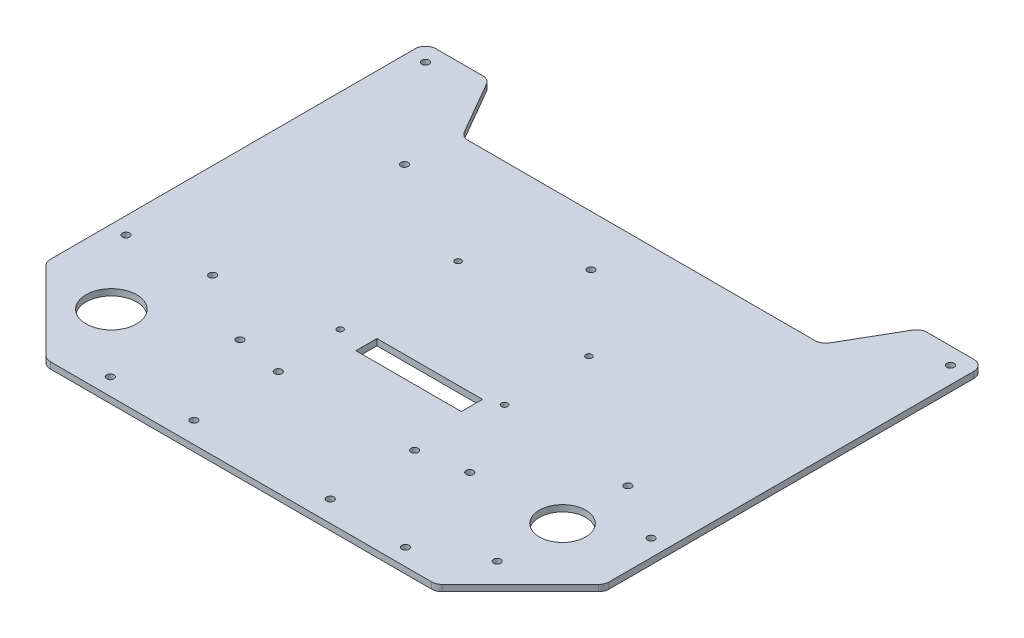
SolidWorks part; units mm, degrees
material "Acier non allié"
ref_plane "Front" through (0, 0, 0) normal (0, 0, 1) x (1, 0, 0)
ref_plane "Top" through (0, 0, 0) normal (0, 1, 0) x (1, 0, 0)
ref_plane "Right" through (0, 0, 0) normal (1, 0, 0) x (0, 0, -1)
sketch "Esquisse1" plane through (0, 0, 0) normal (0, 1, 0) x (1, 0, 0)
  line L0 (0, 0) -> (0, 1919.0564) construction
  line L1 (-92.5, 0) -> (92.5, 0)
  line L2 (92.5, 0) -> (132.5, 40)
  line L3 (132.5, 40) -> (132.5, 220)
  line L4 (132.5, 220) -> (102.5, 220)
  line L5 (102.5, 220) -> (85.1795, 190)
  line L6 (85.1795, 190) -> (-85.1795, 190)
  line L7 (-102.5, 220) -> (-85.1795, 190)
  line L8 (-132.5, 220) -> (-102.5, 220)
  line L9 (-132.5, 40) -> (-132.5, 220)
  line L10 (-92.5, 0) -> (-132.5, 40)
  point P12 (0, 190)
  dimension "D1" = 132.5
  dimension "D2" = 220
  dimension "D3" = 30
  dimension "D4" = 30
  dimension "D5" = 40
  dimension "D6" = 40
  dimension "D7" = 60
extrude "Boss.-Extru.1" add sketch "Esquisse1" along normal blind 3
fillet "Congé1" radius 5 10 edges at (132.5, 1.5, -220) (102.5, 1.5, -220) (85.1795, 1.5, -190) (-85.1795, 1.5, -190) (-102.5, 1.5, -220) (-132.5, 1.5, -220) (-132.5, 1.5, -40) (-92.5, 1.5, 0) (92.5, 1.5, 0) (132.5, 1.5, -40)
sketch "Esquisse2" plane through (0, 0, 0) normal (0, -1, 0) x (1, 0, 0)
  line L0 (0, 0) -> (0, -330.9968) construction
  line L1 (-90.4289, 0) -> (90.4289, 0) construction
  line L2 (-105.3868, -220) -> (-127.5, -220) construction
  line L3 (-132.5, -215) -> (-132.5, -42.0711) construction
  circle A0 centre (-70, -8) radius 1
  circle A1 centre (-124.5, -70) radius 1
  circle A2 centre (-124.5, -212) radius 1
  circle A3 centre (124.5, -212) radius 1
  circle A4 centre (124.5, -70) radius 1
  circle A5 centre (70, -8) radius 1
  dimension "D3" = 2
  dimension "D6" = 2
  dimension "D9" = 2
  dimension "D1" = 70
  dimension "D2" = 8
  dimension "D4" = 124.5
  dimension "D5" = 70
  dimension "D7" = 8
  dimension "D8" = 8
extrude "Enlèv. mat.-Extru.1" cut sketch "Esquisse2" against normal through all
hole_wizard "Dégagement M31" positions "Esquisse3" profile "Esquisse4" hole size "M3" standard "ISO" end condition through all
sketch "Esquisse3" plane through (0, 0, 0) normal (0, -1, 0) x (-1, 0, 0)
  point P0 (-70, 8)
  point P3 (-124.5, 70)
  point P6 (-124.5, 212)
  point P9 (124.5, 212)
  point P12 (124.5, 70)
  point P15 (70, 8)
sketch "Esquisse4" plane through (70, 0, -8) normal (1, 0, 0) x (0, 0, -1)
  line L0 (0, 0) -> (0, 3)
  line L1 (0, 3) -> (1.7, 3)
  line L2 (1.7, 3) -> (1.7, 0)
  line L5 (1.7, 0) -> (0, 0)
  line L11 (0, -6.35) -> (0, 107.95) construction
  dimension "Diamètre du perçage jusqu'au prochain" = 3.4
  dimension "Profondeur du perçage jusqu'au prochain" = 3
sketch "Esquisse5" plane through (0, 0, 0) normal (0, -1, 0) x (1, 0, 0)
  line L0 (-35, -138) -> (-35, -82) construction
  line L5 (35, -130) -> (35, -90) construction
  line L6 (132.5, -42.0711) -> (132.5, -215) construction
  line L7 (97.5, -86) -> (97.5, -24) construction
  line L20 (-132.5, -215) -> (-132.5, -42.0711) construction
  line L21 (-90.4289, 0) -> (90.4289, 0) construction
  line L22 (-105.3868, -220) -> (-127.5, -220) construction
  line L27 (-132.5, -215) -> (-132.5, -42.0711) construction
  line L28 (127.5, -220) -> (105.3868, -220) construction
  line L29 (-54.5, -54) -> (54.5, -54) construction
  line L30 (-54.5, -54) -> (-54.5, -166) construction
  line L31 (-54.5, -166) -> (54.5, -166) construction
  line L32 (54.5, -54) -> (54.5, -166) construction
  line L33 (-87.5, -74) -> (-87.5, -165) construction
  line L34 (-22.5, -87) -> (27.5, -87)
  line L35 (-22.5, -87) -> (-22.5, -77)
  line L36 (-22.5, -77) -> (27.5, -77)
  line L37 (27.5, -87) -> (27.5, -77)
  line L39 (127.5, -220) -> (105.3868, -220) construction
  line L40 (-32.335, -50) -> (32.335, -50) construction
  line L41 (-32.335, -50) -> (-32.335, -10) construction
  line L42 (-32.335, -10) -> (32.335, -10) construction
  line L43 (32.335, -50) -> (32.335, -10) construction
  circle A0 centre (-97.5, -36) radius 12
  circle A3 centre (97.5, -55) radius 11
  circle A4 centre (97.5, -86) radius 1.5
  circle A5 centre (97.5, -24) radius 1.5
  circle A6 centre (-35, -138) radius 1
  circle A7 centre (-35, -82) radius 1
  circle A8 centre (35, -130) radius 1
  circle A9 centre (35, -90) radius 1
  circle A10 centre (0, -166) radius 1.5
  circle A11 centre (-54.5, -54) radius 1.5
  circle A12 centre (54.5, -54) radius 1.5
  circle A13 centre (-87.5, -74) radius 1.5
  circle A14 centre (-87.5, -165) radius 1.5
  circle A15 centre (-32.335, -50) radius 1.5
  circle A16 centre (-32.335, -10) radius 1.5
  circle A17 centre (32.335, -10) radius 1.5
  circle A18 centre (32.335, -50) radius 1.5
  point P8 (97.5, -55)
  point P18 (-35, -110)
  point P23 (0, -166)
  point P29 (54.5, -110)
  point P47 (-22.5, -82)
  point P48 (2.5, -77)
  point P57 (0, 0)
  point P58 (0, -10)
  dimension "D10" = 24
  dimension "D2" = 22
  dimension "D6" = 3
  dimension "D7" = 3
  dimension "D20" = 2
  dimension "D21" = 2
  dimension "D27" = 2
  dimension "D28" = 2
  dimension "D14" = 3
  dimension "D30" = 3
  dimension "D31" = 3
  dimension "D38" = 3
  dimension "D39" = 3
  dimension "D19" = 3
  dimension "D36" = 3
  dimension "D40" = 3
  dimension "D41" = 3
  dimension "D8" = 35
  dimension "D9" = 36
  dimension "D3" = 35
  dimension "D4" = 55
  dimension "D5" = 62
  dimension "D22" = 110
  dimension "D23" = 97.5
  dimension "D24" = 56
  dimension "D25" = 8
  dimension "D26" = 40
  dimension "D29" = 70
  dimension "D11" = 109
  dimension "D12" = 112
  dimension "D13" = 110
  dimension "D32" = 50
  dimension "D33" = 10
  dimension "D34" = 135
  dimension "D35" = 91
  dimension "D37" = 55
  dimension "D15" = 45
  dimension "D16" = 64.67
  dimension "D17" = 40
  dimension "D18" = 10
extrude "Enlèv. mat.-Extru.2" cut sketch "Esquisse5" against normal through all
fillet "Congé2" [suppressed] radius 3
hole_wizard "Dégagement M32" positions "Esquisse6" profile "Esquisse7" hole size "M3" standard "ISO" end condition up to next
sketch "Esquisse6" plane through (0, 3, 0) normal (0, 1, 0) x (1, 0, 0)
  point P7 (97.5, 86)
  point P10 (97.5, 24)
  point P13 (-54.5, 54)
  point P16 (54.5, 54)
  point P19 (0, 166)
  point P24 (-87.5, 74)
  point P27 (-87.5, 165)
  point P30 (-32.335, 50)
  point P33 (-32.335, 10)
  point P36 (32.335, 10)
  point P39 (32.335, 50)
sketch "Esquisse7" plane through (97.5, 3, -86) normal (1, 0, 0) x (0, 0, 1)
  line L0 (0, 0) -> (0, 3)
  line L1 (0, 3) -> (1.7, 3)
  line L2 (1.7, 3) -> (1.7, 0)
  line L5 (1.7, 0) -> (0, 0)
  line L11 (0, -6.35) -> (0, 107.95) construction
  dimension "Diamètre du perçage jusqu'au prochain" = 3.4
  dimension "Profondeur du perçage jusqu'au prochain" = 3
hole_wizard "Dégagement M2.51" positions "Esquisse8" profile "Esquisse9" hole size "M2.5" standard "ISO" end condition up to next
sketch "Esquisse8" plane through (0, 3, 0) normal (0, 1, 0) x (1, 0, 0)
  point P0 (-35, 138)
  point P3 (-35, 82)
  point P6 (35, 90)
  point P9 (35, 130)
sketch "Esquisse9" plane through (-35, 3, -138) normal (1, 0, 0) x (0, 0, 1)
  line L0 (0, 0) -> (0, 3)
  line L1 (0, 3) -> (1.45, 3)
  line L2 (1.45, 3) -> (1.45, 0)
  line L5 (1.45, 0) -> (0, 0)
  line L11 (0, -6.35) -> (0, 107.95) construction
  dimension "Diamètre du perçage jusqu'au prochain" = 2.9
  dimension "Profondeur du perçage jusqu'au prochain" = 3
sketch "Esquisse10" plane through (0, 3, 0) normal (0, 1, 0) x (1, 0, 0)
  line L3 (-57.5, 38) -> (57.5, 38) construction
  line L4 (-132.5, 215) -> (-132.5, 42.0711) construction
  line L5 (132.5, 42.0711) -> (132.5, 215) construction
  line L6 (-90.4289, 0) -> (90.4289, 0) construction
  text T0 "TUTANKHABOT"
  text T1 "\r\nDesigned and assembled by :\r\n" font "Century Gothic" height in points 14
  text T2 "\r\n\r\nBERNARD Théau\r\nBOSSCHAERT Sébastien\r\nBOULANGER François\r\n" font "Century Gothic" height in points 14
  text T3 "\r\n\r\nISENGUERRE Nicolas\r\nLANNOEY Diego\r\nMERCIER Clément" font "Century Gothic" height in points 14
  dimension "D1" = 75
  dimension "D2" = 75
  dimension "D3" = 38
extrude "Enlèv. mat.-Extru.3" [suppressed] cut sketch "Esquisse10" against normal blind 0.1
equation "\"WIDTH\"= 300mm'Total width of the robot"
equation "\"LENGTH\"= 220mm'Total length of the robot"
equation "\"CUT_DEPTH\"= 45mm'Depth of the cut on the edges of the plate"
equation "\"Plate_th\"= 3mm'Thickness of the plate"
equation "\"D1\"= \"Plate_th\""
equation "\"D23@Esquisse5\"=(265-70)/2"
